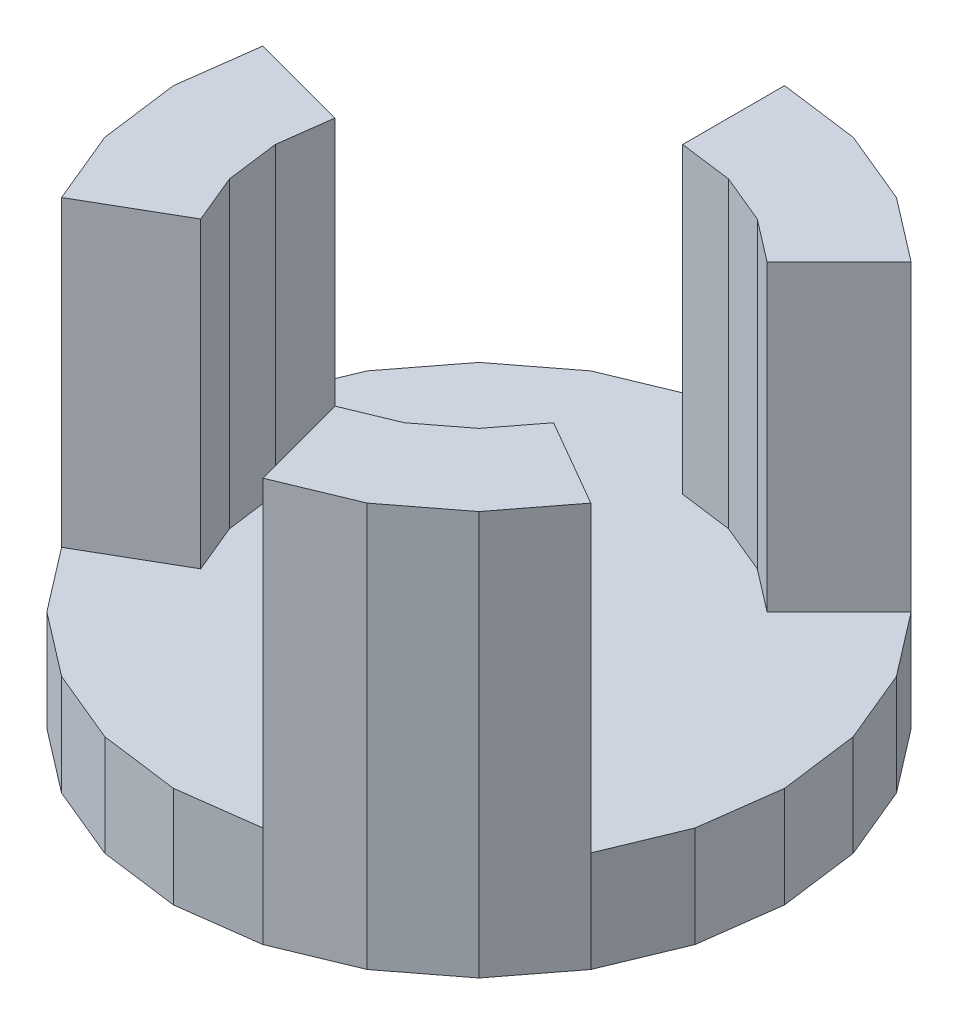
SolidWorks part; units mm, degrees
ref_plane "Front Plane" through (0, 0, 0) normal (0, 0, 1) x (1, 0, 0)
ref_plane "Top Plane" through (0, 0, 0) normal (0, 1, 0) x (1, 0, 0)
ref_plane "Right Plane" through (0, 0, 0) normal (1, 0, 0) x (0, 0, -1)
sketch "Sketch1" plane through (0, 0, 0) normal (0, 1, 0) x (1, 0, 0)
  line L0 (0, 20.1726) -> (0, 30.2589)
  line L1 (30.2589, 0) -> (29.2278, 7.8316)
  line L2 (29.2278, 7.8316) -> (26.2049, 15.1294)
  line L3 (26.2049, 15.1294) -> (21.3963, 21.3963)
  line L4 (21.3963, 21.3963) -> (15.1294, 26.2049)
  line L5 (15.1294, 26.2049) -> (7.8316, 29.2278)
  line L6 (7.8316, 29.2278) -> (0, 30.2589)
  line L7 (0, 30.2589) -> (-7.8316, 29.2278)
  line L8 (-7.8316, 29.2278) -> (-15.1294, 26.2049)
  line L9 (-15.1294, 26.2049) -> (-21.3963, 21.3963)
  line L10 (-21.3963, 21.3963) -> (-26.2049, 15.1294)
  line L11 (-26.2049, 15.1294) -> (-29.2278, 7.8316)
  line L12 (-29.2278, 7.8316) -> (-30.2589, 0)
  line L13 (-30.2589, 0) -> (-29.2278, -7.8316)
  line L14 (-29.2278, -7.8316) -> (-26.2049, -15.1294)
  line L15 (-26.2049, -15.1294) -> (-21.3963, -21.3963)
  line L16 (-21.3963, -21.3963) -> (-15.1294, -26.2049)
  line L17 (-15.1294, -26.2049) -> (-7.8316, -29.2278)
  line L18 (-7.8316, -29.2278) -> (0, -30.2589)
  line L19 (0, -30.2589) -> (7.8316, -29.2278)
  line L20 (7.8316, -29.2278) -> (15.1294, -26.2049)
  line L21 (15.1294, -26.2049) -> (21.3963, -21.3963)
  line L22 (21.3963, -21.3963) -> (26.2049, -15.1294)
  line L23 (26.2049, -15.1294) -> (29.2278, -7.8316)
  line L24 (29.2278, -7.8316) -> (30.2589, 0)
  line L25 (20.1726, 0) -> (19.4852, 5.221)
  line L26 (19.4852, 5.221) -> (17.47, 10.0863)
  line L27 (17.47, 10.0863) -> (14.2642, 14.2642)
  line L28 (14.2642, 14.2642) -> (10.0863, 17.47)
  line L29 (10.0863, 17.47) -> (5.221, 19.4852)
  line L30 (5.221, 19.4852) -> (0, 20.1726)
  line L31 (0, 20.1726) -> (-5.221, 19.4852)
  line L32 (-5.221, 19.4852) -> (-10.0863, 17.47)
  line L33 (-10.0863, 17.47) -> (-14.2642, 14.2642)
  line L34 (-14.2642, 14.2642) -> (-17.47, 10.0863)
  line L35 (-17.47, 10.0863) -> (-19.4852, 5.221)
  line L36 (-19.4852, 5.221) -> (-20.1726, 0)
  line L37 (-20.1726, 0) -> (-19.4852, -5.221)
  line L38 (-19.4852, -5.221) -> (-17.47, -10.0863)
  line L39 (-17.47, -10.0863) -> (-14.2642, -14.2642)
  line L40 (-14.2642, -14.2642) -> (-10.0863, -17.47)
  line L41 (-10.0863, -17.47) -> (-5.221, -19.4852)
  line L42 (-5.221, -19.4852) -> (0, -20.1726)
  line L43 (0, -20.1726) -> (5.221, -19.4852)
  line L44 (5.221, -19.4852) -> (10.0863, -17.47)
  line L45 (10.0863, -17.47) -> (14.2642, -14.2642)
  line L46 (14.2642, -14.2642) -> (17.47, -10.0863)
  line L47 (17.47, -10.0863) -> (19.4852, -5.221)
  line L48 (19.4852, -5.221) -> (20.1726, 0)
  line L49 (14.2642, 14.2642) -> (21.3963, 21.3963)
  line L50 (17.47, -10.0863) -> (26.2049, -15.1294)
  line L51 (5.221, -19.4852) -> (7.8316, -29.2278)
  line L52 (-17.47, -10.0863) -> (-26.2049, -15.1294)
  line L53 (-19.4852, 5.221) -> (-29.2278, 7.8316)
  line L54 (-1.5, 1.3229) -> (1.5, 1.3229)
  circle A0 centre (0, 0) radius 30 construction
  circle A1 centre (0, 0) radius 20 construction
  circle A2 centre (0, 0) radius 2
  dimension "D3" = 4
  dimension "D1" = 20
  dimension "D2" = 30
  dimension "D4" = 3
extrude "Boss-Extrude3" add sketch "Sketch1" along normal blind 40 contours L28 L49 L4 L5 L6 L0 L30 L29 | L44 L51 L20 L21 L22 L50 L46 L45 | L36 L53 L12 L13 L14 L52 L38 L37 region at (9.4744, 0, -22.8733) region at (-24.5461, 0, 3.2315) region at (15.0716, 0, 19.6417)
extrude "Boss-Extrude4" add sketch "Sketch1<6>" along normal blind 10 contours L47 L50 L23 L24 L1 L2 L3 L49 L27 L26 L25 L48 | L53 L35 L34 L33 L32 L31 L0 L7 L8 L9 L10 L11 | L39 L52 L15 L16 L17 L18 L19 L51 L43 L42 L41 L40 | L47 L48 L25 L26 L27 L28 L29 L30 L31 L32 L33 L34 L35 L36 L37 L38 L39 L40 L41 L42 L43 L44 L45 L46 A2 | L54 A2 region at (-14.3853, 0, -18.7473) region at (2.536, 0, -19.2632) region at (23.4283, 0, -3.0844) region at (-9.043, 0, 21.8317) region at (0, 0, -1.5981)
sketch "Sketch1<6>" plane through (0, 0, 0) normal (0, 1, 0) x (1, 0, 0) same geometry as "Sketch1"
